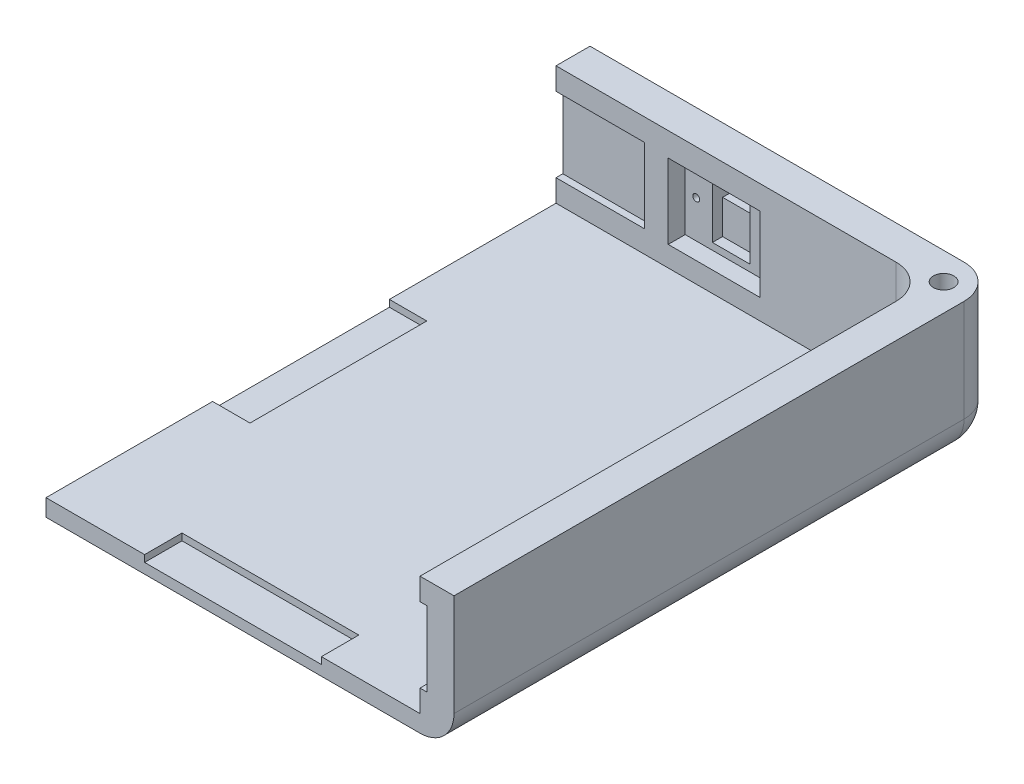
SolidWorks part; units mm, degrees
ref_plane "Plan de face" through (0, 0, 0) normal (0, 0, 1) x (1, 0, 0)
ref_plane "Plan de dessus" through (0, 0, 0) normal (0, 1, 0) x (1, 0, 0)
ref_plane "Plan de droite" through (0, 0, 0) normal (1, 0, 0) x (0, 0, -1)
sketch "Esquisse1" plane through (0, 0, 0) normal (0, 1, 0) x (1, 0, 0)
  line L1 (0, 0) -> (120, 0)
  line L2 (0, 0) -> (0, 160)
  line L3 (0, 160) -> (120, 160)
  line L4 (120, 0) -> (120, 160)
  dimension "D1" = 120
  dimension "D2" = 160
extrude "Boss.-Extru.1" add sketch "Esquisse1" along normal blind 40
fillet "Congé1" radius 10 1 edges at (60, 0, -160)
fillet "Congé2" radius 10 3 edges at (120, 25, -160) (120, 2.9289, -157.0711) (120, 0, -75)
sketch "Esquisse2" plane through (0, 40, 0) normal (0, 1, 0) x (1, 0, 0)
  line L0 (110, 160) -> (0, 160) construction
  line L1 (0, 0) -> (110, 0)
  line L2 (0, 0) -> (0, 150)
  line L3 (0, 150) -> (110, 150)
  line L4 (110, 0) -> (110, 150)
  line L5 (120, 0) -> (120, 150) construction
  dimension "D1" = 10
  dimension "D2" = 10
extrude "Enlèv. mat.-Extru.1" cut sketch "Esquisse2" against normal blind 35
fillet "Congé3" radius 10 1 edges at (110, 22.5, -150)
sketch "Esquisse3" plane through (0, 40, 0) normal (0, 1, 0) x (1, 0, 0)
  line L0 (110, 160) -> (0, 160) construction
  line L1 (120, 0) -> (120, 150) construction
  circle A0 centre (112, 152) radius 3
  dimension "D3" = 6
  dimension "D1" = 8
  dimension "D2" = 8
extrude "Enlèv. mat.-Extru.2" cut sketch "Esquisse3" against normal blind 35
sketch "Esquisse4" plane through (0, 0, 0) normal (0, -1, 0) x (1, 0, 0)
  line L0 (110, -150) -> (110, 0) construction
  line L1 (0, -150) -> (110, -150) construction
  circle A0 centre (90, -130) radius 2.5
  dimension "D3" = 5
  dimension "D1" = 20
  dimension "D2" = 20
extrude "Boss.-Extru.2" add sketch "Esquisse4" along normal blind 2.5
fillet "Congé4" radius 2.5 1 edges at (90, -2.5, -132.5)
sketch "Esquisse5" plane through (0, 5, 0) normal (0, 1, 0) x (1, 0, 0)
  line L0 (0, 150) -> (0, 0) construction
  line L1 (0, 101) -> (11, 101)
  line L2 (0, 101) -> (0, 49)
  line L3 (0, 49) -> (11, 49)
  line L4 (11, 101) -> (11, 49)
  line L5 (0, 0) -> (110, 0) construction
  line L6 (81, 0) -> (29, 0)
  line L7 (81, 0) -> (81, 11)
  line L8 (81, 11) -> (29, 11)
  line L9 (29, 0) -> (29, 11)
  line L10 (100, 150) -> (0, 150) construction
  line L12 (110, 0) -> (110, 140) construction
  point P14 (5.5, 101)
  point P17 (81, 5.5)
  dimension "D1" = 49
  dimension "D2" = 49
  dimension "D3" = 11
  dimension "D4" = 29
  dimension "D5" = 29
  dimension "D6" = 11
extrude "Enlèv. mat.-Extru.3" cut sketch "Esquisse5" against normal blind 2
sketch "Esquisse6" plane through (0, 0, -150) normal (0, 0, 1) x (1, 0, 0)
  line L0 (0, 5) -> (0, 40) construction
  line L1 (0, 33.5) -> (26, 33.5)
  line L2 (0, 33.5) -> (0, 11.5)
  line L3 (0, 11.5) -> (26, 11.5)
  line L4 (26, 33.5) -> (26, 11.5)
  line L5 (100, 40) -> (0, 40) construction
  line L6 (100, 5) -> (0, 5) construction
  dimension "D1" = 6.5
  dimension "D2" = 6.5
  dimension "D3" = 26
extrude "Enlèv. mat.-Extru.4" cut sketch "Esquisse6" against normal blind 2
sketch "Esquisse7" plane through (110, 0, 0) normal (-1, 0, 0) x (0, 0, 1)
  line L0 (0, 5) -> (0, 40) construction
  line L1 (0, 33.5) -> (-26, 33.5)
  line L2 (0, 33.5) -> (0, 11.5)
  line L3 (0, 11.5) -> (-26, 11.5)
  line L4 (-26, 33.5) -> (-26, 11.5)
  line L5 (0, 5) -> (-140, 5) construction
  line L6 (0, 40) -> (-140, 40) construction
  dimension "D1" = 6.5
  dimension "D2" = 6.5
  dimension "D3" = 26
extrude "Enlèv. mat.-Extru.5" cut sketch "Esquisse7" against normal blind 2
sketch "Esquisse8" plane through (0, 0, -150) normal (0, 0, 1) x (1, 0, 0)
  line L0 (100, 5) -> (100, 40) construction
  line L1 (60, 33) -> (33, 33)
  line L2 (60, 33) -> (60, 11)
  line L3 (60, 11) -> (33, 11)
  line L4 (33, 33) -> (33, 11)
  line L5 (100, 5) -> (0, 5) construction
  dimension "D1" = 40
  dimension "D2" = 27
  dimension "D3" = 22
  dimension "D4" = 6
extrude "Enlèv. mat.-Extru.6" cut sketch "Esquisse8" against normal blind 5
sketch "Esquisse9" plane through (0, 0, -155) normal (0, 0, 1) x (1, 0, 0)
  line L0 (60, 11) -> (60, 33) construction
  line L1 (33, 11) -> (60, 11) construction
  circle A0 centre (56.75, 22) radius 1
  circle A1 centre (36.25, 22) radius 1
  dimension "D1" = 2
  dimension "D2" = 2
  dimension "D3" = 23.75
  dimension "D4" = 3.25
  dimension "D5" = 11
  dimension "D6" = 11
extrude "Enlèv. mat.-Extru.7" cut sketch "Esquisse9" against normal blind 4
sketch "Esquisse10" plane through (0, 0, -155) normal (0, 0, 1) x (1, 0, 0)
  line L0 (60, 33) -> (33, 33) construction
  line L1 (52, 29) -> (41, 29)
  line L2 (52, 29) -> (52, 23)
  line L3 (52, 23) -> (41, 23)
  line L4 (41, 29) -> (41, 23)
  line L5 (60, 11) -> (60, 33) construction
  dimension "D1" = 4
  dimension "D2" = 6
  dimension "D3" = 11
  dimension "D4" = 8
extrude "Enlèv. mat.-Extru.8" cut sketch "Esquisse10" against normal through all
sketch "Esquisse11" plane through (0, 0, -155) normal (0, 0, 1) x (1, 0, 0)
  line L0 (33, 11) -> (60, 11) construction
  line L1 (41, 23) -> (52, 23)
  line L2 (41, 23) -> (41, 13)
  line L3 (41, 13) -> (52, 13)
  line L4 (52, 23) -> (52, 13)
  dimension "D1" = 2
  dimension "D2" = 11
extrude "Enlèv. mat.-Extru.9" cut sketch "Esquisse11" against normal blind 3
